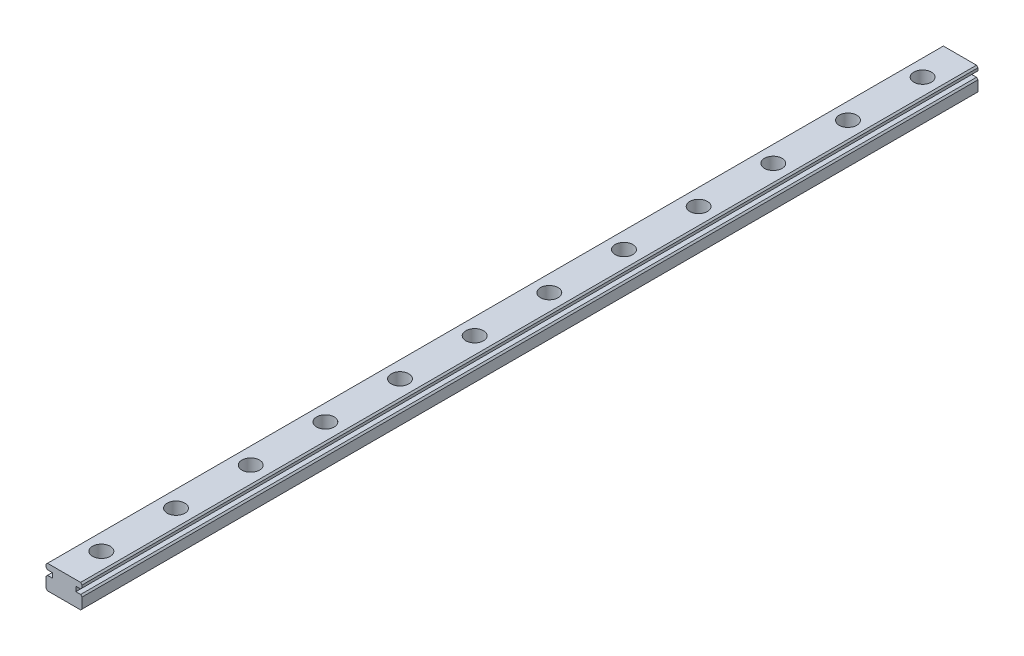
SolidWorks part; units mm, degrees
ref_plane "Front Plane" through (0, 0, 0) normal (0, 0, 1) x (1, 0, 0)
ref_plane "Top Plane" through (0, 0, 0) normal (0, 1, 0) x (1, 0, 0)
ref_plane "Right Plane" through (0, 0, 0) normal (1, 0, 0) x (0, 0, -1)
sketch "Sketch1" plane through (0, 0, 0) normal (0, 0, 1) x (1, 0, 0)
  line L0 (6.05, 2.1) -> (3.95, 2.1)
  line L1 (-6.05, 4) -> (6.05, 4)
  line L2 (-6.05, 4) -> (-6.05, 2.1)
  line L3 (-6.05, -4) -> (6.05, -4)
  line L4 (6.05, 4) -> (6.05, 2.1)
  line L5 (-6.05, 4) -> (6.05, -4) construction
  line L6 (-6.05, -4) -> (6.05, 4) construction
  line L7 (3.95, 2.1) -> (3.95, 0.5)
  line L8 (3.95, 0.5) -> (6.05, 0.5)
  line L9 (0, 0) -> (0, 2.5782)
  line L10 (-3.95, 0.5) -> (-6.05, 0.5)
  line L11 (-3.95, 2.1) -> (-3.95, 0.5)
  line L12 (-6.05, 2.1) -> (-3.95, 2.1)
  line L13 (-6.05, 0.5) -> (-6.05, -4)
  line L14 (6.05, 0.5) -> (6.05, -4)
  point P0 (0, 0)
  dimension "D1" = 12.1
  dimension "D2" = 8
  dimension "D3" = 1.9
  dimension "D4" = 1.6
  dimension "D5" = 2.1
extrude "Boss-Extrude1" add sketch "Sketch1" along normal blind 300 contours L14 L8 L7 L0 L4 L1 L2 L12 L11 L10 L13 L3 region at (0, -0.097, 0)
chamfer "Chamfer1" distance 0.5 angle 45 8 edges at (6.05, -4, 150) (-6.05, -4, 150) (-6.05, 0.5, 150) (-6.05, 2.1, 150) (-6.05, 4, 150) (6.05, 4, 150) (6.05, 2.1, 150) (6.05, 0.5, 150)
sketch "Sketch2" plane through (0, -4, 0) normal (0, -1, 0) x (1, 0, 0)
  line L0 (-5.55, 150) -> (5.55, 150)
  line L4 (-5.55, 0) -> (5.55, 0)
  line L5 (5.55, 0) -> (5.55, 300)
  line L6 (5.55, 300) -> (-5.55, 300)
  line L7 (-5.55, 300) -> (-5.55, 0)
  line L8 (-5.55, 0) -> (5.55, 0)
  line L9 (5.55, 0) -> (5.55, 300)
  line L10 (5.55, 300) -> (-5.55, 300)
  line L11 (-5.55, 300) -> (-5.55, 0)
  circle A0 centre (0, 137.5) radius 1.6
  circle A1 centre (0, 162.5) radius 1.6
  circle A2 centre (0, 112.5) radius 1.6
  circle A3 centre (0, 187.5) radius 1.6
  circle A4 centre (0, 87.5) radius 1.6
  circle A5 centre (0, 212.5) radius 1.6
  circle A6 centre (0, 62.5) radius 1.6
  circle A7 centre (0, 237.5) radius 1.6
  circle A8 centre (0, 262.5) radius 1.6
  circle A9 centre (0, 287.5) radius 1.6
  circle A10 centre (0, 37.5) radius 1.6
  circle A11 centre (0, 12.5) radius 1.6
  dimension "D4" = 3.2
  dimension "D5" = 3.2
  dimension "D2" = 12.5
  dimension "D3" = 12.5
  dimension "D6" = 37.5
  dimension "D7" = 37.5
  dimension "D8" = 62.5
  dimension "D9" = 62.5
  dimension "D10" = 87.5
  dimension "D11" = 87.5
  dimension "D12" = 25
  dimension "D13" = 25
  dimension "D14" = 25
  dimension "D15" = 25
  dimension "D1" = 0
extrude "Cut-Extrude1" cut sketch "Sketch2" against normal blind 200 contours A6 | A4 | A2 | A0 | A1 | A3 | A5 | A7 | A9 | A8 | A10 | A11 region at (0, -4, 137.5) region at (0, -4, 162.5) region at (0, -4, 112.5) region at (0, -4, 187.5) region at (0, -4, 87.5) region at (0, -4, 62.5)
sketch "Sketch3" plane through (0, 4, 0) normal (0, 1, 0) x (1, 0, 0)
  circle A0 centre (0, -237.5) radius 2.95
  circle A1 centre (0, -187.5) radius 2.95
  circle A2 centre (0, -112.5) radius 2.95
  circle A3 centre (0, -212.5) radius 2.95
  circle A4 centre (0, -162.5) radius 2.95
  circle A5 centre (0, -137.5) radius 2.95
  circle A6 centre (0, -62.5) radius 2.95
  circle A7 centre (0, -87.5) radius 2.95
  circle A8 centre (0, -262.5) radius 2.95
  circle A9 centre (0, -287.5) radius 2.95
  circle A10 centre (0, -12.5) radius 2.95
  circle A11 centre (0, -37.5) radius 2.95
  circle M10 centre (0, -112.5) radius 1.6
  circle M11 centre (0, -137.5) radius 1.6
  circle M12 centre (0, -162.5) radius 1.6
  circle M13 centre (0, -187.5) radius 1.6
  circle M14 centre (0, -212.5) radius 1.6
  circle M15 centre (0, -237.5) radius 1.6
  circle M24 centre (0, -12.5) radius 1.6
  dimension "D1" = 5.9
extrude "Cut-Extrude2" cut sketch "Sketch3" against normal blind 5.6 contours A0 M15 | A3 M14 | A1 M13 | A4 M12 | A5 M11 | A2 M10 | A10 M24 | A7 | A6 | A8 | A9 | A11 region at (-2.8666, 4, 237.5) region at (-2.8666, 4, 187.5) region at (-2.8666, 4, 112.5) region at (-2.8666, 4, 212.5) region at (-2.8666, 4, 162.5) region at (-2.8666, 4, 137.5) region at (-2.8666, 4, 12.5)
sketch "Sketch4" plane through (0, 0, 0) normal (0, 0, -1) x (-1, 0, 0)
  line L20 (-6.05, 0) -> (-6.05, -3.5)
  line L21 (-6.05, -3.5) -> (-5.55, -4)
  line L22 (-5.55, -4) -> (5.55, -4)
  line L23 (5.55, -4) -> (6.05, -3.5)
  line L24 (6.05, -3.5) -> (6.05, 0)
  line L25 (6.05, 0) -> (5.55, 0.5)
  line L26 (5.55, 0.5) -> (3.95, 0.5)
  line L27 (3.95, 0.5) -> (3.95, 2.1)
  line L28 (3.95, 2.1) -> (5.55, 2.1)
  line L29 (5.55, 2.1) -> (6.05, 2.6)
  line L30 (6.05, 2.6) -> (6.05, 3.5)
  line L31 (6.05, 3.5) -> (5.55, 4)
  line L32 (5.55, 4) -> (-5.55, 4)
  line L33 (-5.55, 4) -> (-6.05, 3.5)
  line L34 (-6.05, 3.5) -> (-6.05, 2.6)
  line L35 (-6.05, 2.6) -> (-5.55, 2.1)
  line L36 (-5.55, 2.1) -> (-3.95, 2.1)
  line L37 (-3.95, 2.1) -> (-3.95, 0.5)
  line L38 (-3.95, 0.5) -> (-5.55, 0.5)
  line L39 (-5.55, 0.5) -> (-6.05, 0)
  line L40 (-6.05, 0) -> (-6.05, -3.5)
  line L41 (-6.05, -3.5) -> (-5.55, -4)
  line L42 (-5.55, -4) -> (5.55, -4)
  line L43 (5.55, -4) -> (6.05, -3.5)
  line L44 (6.05, -3.5) -> (6.05, 0)
  line L45 (6.05, 0) -> (5.55, 0.5)
  line L46 (5.55, 0.5) -> (3.95, 0.5)
  line L47 (3.95, 0.5) -> (3.95, 2.1)
  line L48 (3.95, 2.1) -> (5.55, 2.1)
  line L49 (5.55, 2.1) -> (6.05, 2.6)
  line L50 (6.05, 2.6) -> (6.05, 3.5)
  line L51 (6.05, 3.5) -> (5.55, 4)
  line L52 (5.55, 4) -> (-5.55, 4)
  line L53 (-5.55, 4) -> (-6.05, 3.5)
  line L54 (-6.05, 3.5) -> (-6.05, 2.6)
  line L55 (-6.05, 2.6) -> (-5.55, 2.1)
  line L56 (-5.55, 2.1) -> (-3.95, 2.1)
  line L57 (-3.95, 2.1) -> (-3.95, 0.5)
  line L58 (-3.95, 0.5) -> (-5.55, 0.5)
  line L59 (-5.55, 0.5) -> (-6.05, 0)
  dimension "D1" = 0
sketch "Sketch5" plane through (0, 4, 0) normal (0, 1, 0) x (1, 0, 0)
  circle A0 centre (0, -237.5) radius 2.95 construction
  circle A1 centre (0, -212.5) radius 2.95 construction
  circle A2 centre (0, -187.5) radius 2.95 construction
  circle A3 centre (0, -162.5) radius 2.95 construction
  circle A4 centre (0, -137.5) radius 2.95 construction
  circle A5 centre (0, -112.5) radius 2.95 construction
  circle A6 centre (0, -87.5) radius 2.95 construction
  circle A7 centre (0, -62.5) radius 2.95 construction
  circle A8 centre (0, -237.5) radius 2.95
  circle A9 centre (0, -212.5) radius 2.95
  circle A10 centre (0, -187.5) radius 2.95
  circle A11 centre (0, -162.5) radius 2.95
  circle A12 centre (0, -137.5) radius 2.95
  circle A13 centre (0, -112.5) radius 2.95
  circle A14 centre (0, -87.5) radius 2.95
  circle A15 centre (0, -62.5) radius 2.95
equation "\"length\"= 300mm"
equation "\"D1@Boss-Extrude1\"=\"length\""
